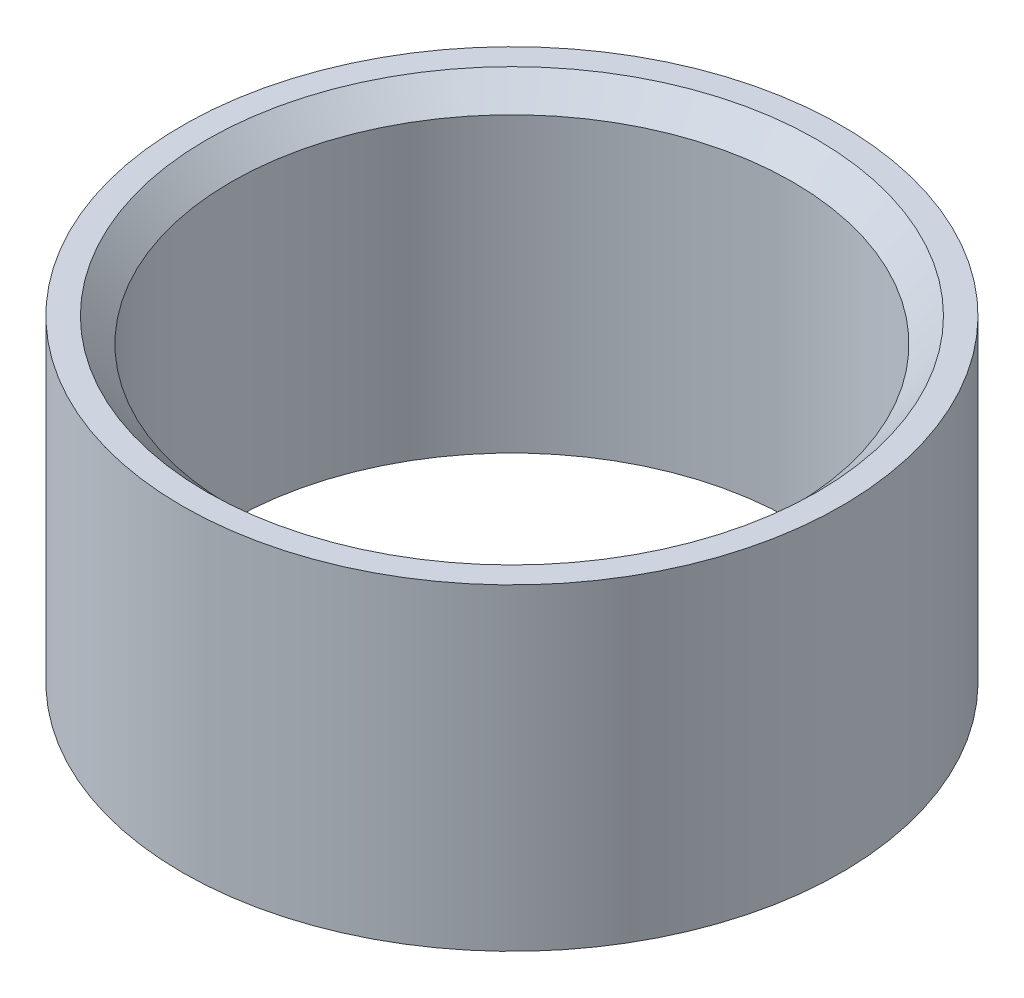
SolidWorks part; units mm, degrees
ref_plane "Front Plane" through (0, 0, 0) normal (0, 0, 1) x (1, 0, 0)
ref_plane "Top Plane" through (0, 0, 0) normal (0, 1, 0) x (1, 0, 0)
ref_plane "Right Plane" through (0, 0, 0) normal (1, 0, 0) x (0, 0, -1)
sketch "Sketch1" plane through (0, 0, 0) normal (0, 1, 0) x (1, 0, 0)
  circle A0 centre (0, 0) radius 1.35
  dimension "D1" = 2.7
extrude "Boss-Extrude1" add sketch "Sketch1" along normal blind 1.3
hole_wizard "Ø2.3 (2.3) Diameter Hole1" positions "Sketch4" profile "Sketch3" hole size "Ø2.3" standard "ANSI Metric" end condition up to next
sketch "Sketch4" plane through (0, 1.3, 0) normal (0, 1, 0) x (1, 0, 0)
  point P0 (0, 0)
sketch "Sketch3" plane through (0, 1.3, 0) normal (1, 0, 0) x (0, 0, 1)
  line L0 (0, 0) -> (0, 1.3)
  line L1 (0, 1.3) -> (1.15, 1.3)
  line L2 (1.15, 1.3) -> (1.15, 0.1)
  line L3 (1.15, 0.1) -> (1.25, 0)
  line L5 (1.25, 0) -> (0, 0)
  line L6 (-1.15, 0.1) -> (-1.25, 0) construction
  line L11 (0, -6.35) -> (0, 107.95) construction
  dimension "Thru Hole Dia." = 2.3
  dimension "Thru Hole Depth" = 1.3
  dimension "Near C'Sink Dia." = 2.5
  dimension "Near C'Sink Angle" = 90
